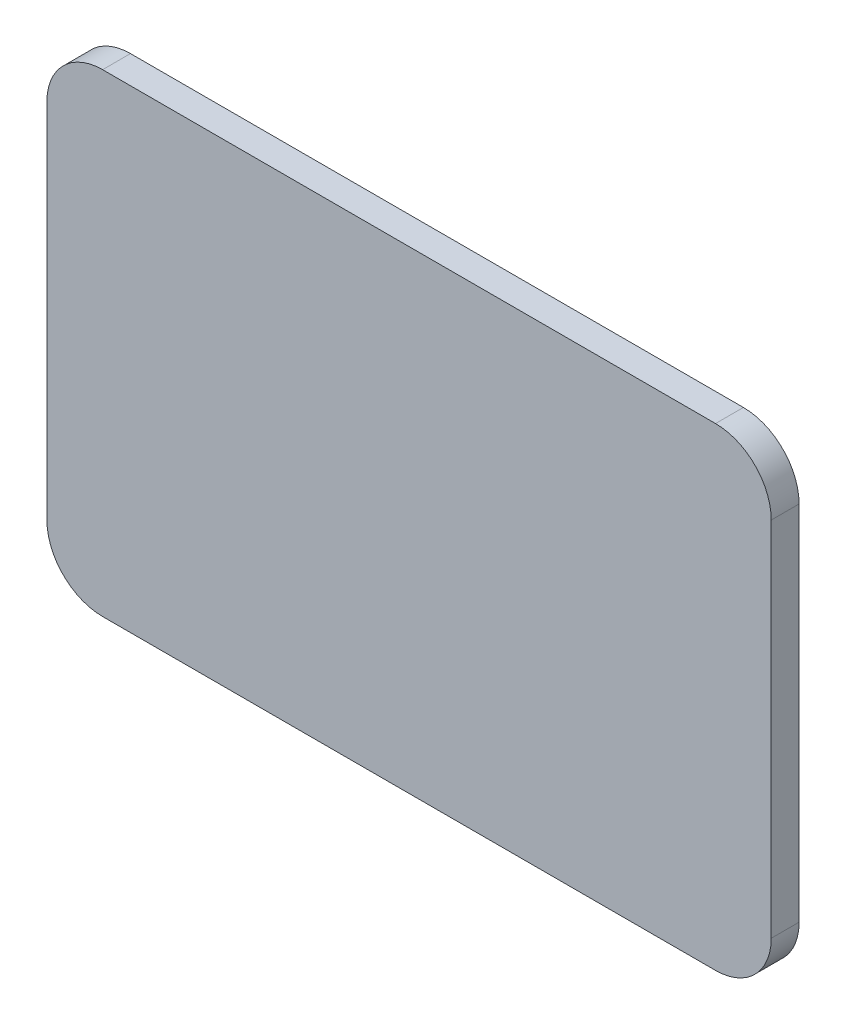
SolidWorks part; units mm, degrees
ref_plane "前视基准面" through (0, 0, 0) normal (0, 0, 1) x (1, 0, 0)
ref_plane "上视基准面" through (0, 0, 0) normal (0, 1, 0) x (1, 0, 0)
ref_plane "右视基准面" through (0, 0, 0) normal (1, 0, 0) x (0, 0, -1)
other "Configuration Table"
sketch "草图1" plane through (0, 0, 0) normal (0, 0, 1) x (1, 0, 0)
  line L0 (0, 0) -> (26, 0)
  line L1 (26, 0) -> (26, 17)
  line L2 (26, 17) -> (0, 17)
  line L3 (0, 17) -> (0, 0)
  dimension "width" = 26
  dimension "height" = 17
extrude "BlockExtrude" add sketch "草图1" along normal blind 1
fillet "Fillet" radius 2 4 edges at (0, 17, 0.5) (26, 17, 0.5) (26, 0, 0.5) (0, 0, 0.5) tangent propagation no
